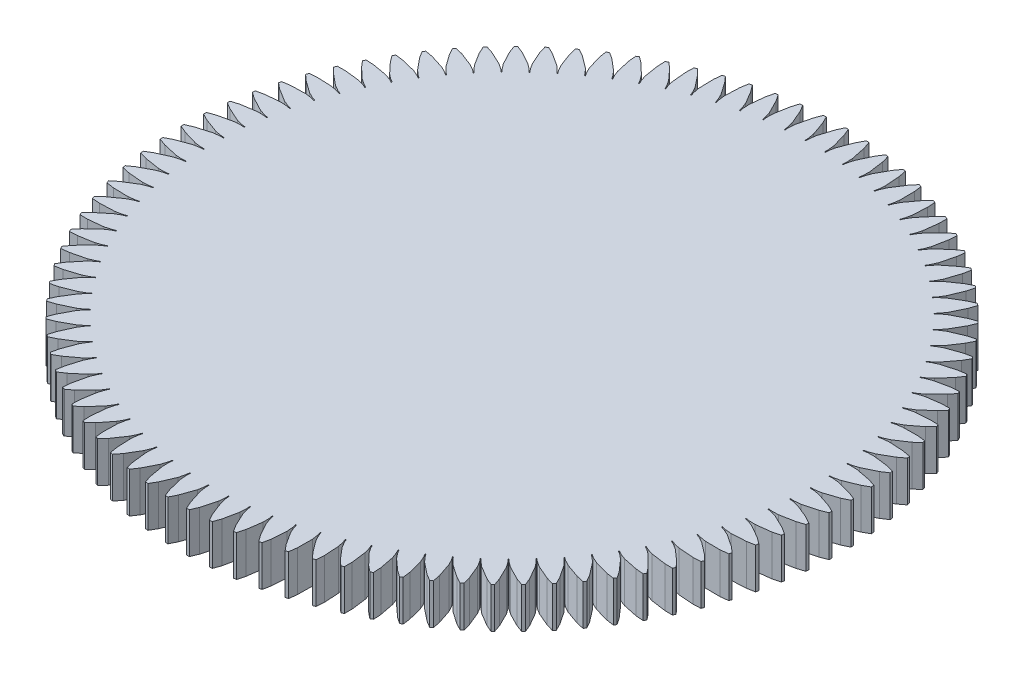
SolidWorks part; units mm, degrees
ref_plane "Plan de face" through (0, 0, 0) normal (0, 0, 1) x (1, 0, 0)
ref_plane "Plan de dessus" through (0, 0, 0) normal (0, 1, 0) x (1, 0, 0)
ref_plane "Plan de droite" through (0, 0, 0) normal (1, 0, 0) x (0, 0, -1)
sketch "Esquisse1" plane through (0, 0, 0) normal (0, 1, 0) x (1, 0, 0)
  line L0 (-22.3282, 0.7042) -> (-22.78, 0.6445)
  line L1 (-22.78, 0.6445) -> (-23.8343, 0.3312)
  line L2 (-23.8343, 0.3312) -> (-24.3609, 0.1004)
  line L3 (-24.3609, 0.1004) -> (-24.3609, -0.1004)
  line L4 (-24.3609, -0.1004) -> (-23.8343, -0.3312)
  line L5 (-23.8343, -0.3312) -> (-22.78, -0.6445)
  line L6 (-22.78, -0.6445) -> (-22.3282, -0.7042)
  line L7 (-22.3282, -0.7042) -> (-22.0374, -0.7042)
  line L8 (-22.3282, 0.7042) -> (-22.0374, 0.7042)
  line L9 (-49.7833, 0) -> (-43.9352, 0) construction
  circle A0 centre (0, 0) radius 24.3611 construction
  arc A1 (-22.0374, 0.7042) -> (-22.0374, -0.7042) centre (0, 0) ccw
  dimension "D1" = 0.6623
  dimension "D2" = 1.289
  dimension "D3" = 1.4084
  dimension "D4" = 0.2009
  dimension "D5" = 0.5266
  dimension "D6" = 1.5809
  dimension "D7" = 2.0327
  dimension "D8" = 2.3234
extrude "Boss.-Extru.1" add sketch "Esquisse1" along normal blind 3
sketch "Esquisse2" plane through (0, 0, 0) normal (0, 1, 0) x (1, 0, 0)
  circle A0 centre (0, 0) radius 22.0487
  arc A1 (-22.0374, 0.7042) -> (-22.0374, -0.7042) centre (0, 0) ccw construction
  point P0 (0, 0)
extrude "Boss.-Extru.2" add sketch "Esquisse2" along normal up to surface (3 mm away) up to face at (-23.0693, 3, 0)
pattern_circular "Répétition circulaire1" count 95 over 360 about axis through (0, 3, 0) along (0, 1, 0) of "Boss.-Extru.1"
